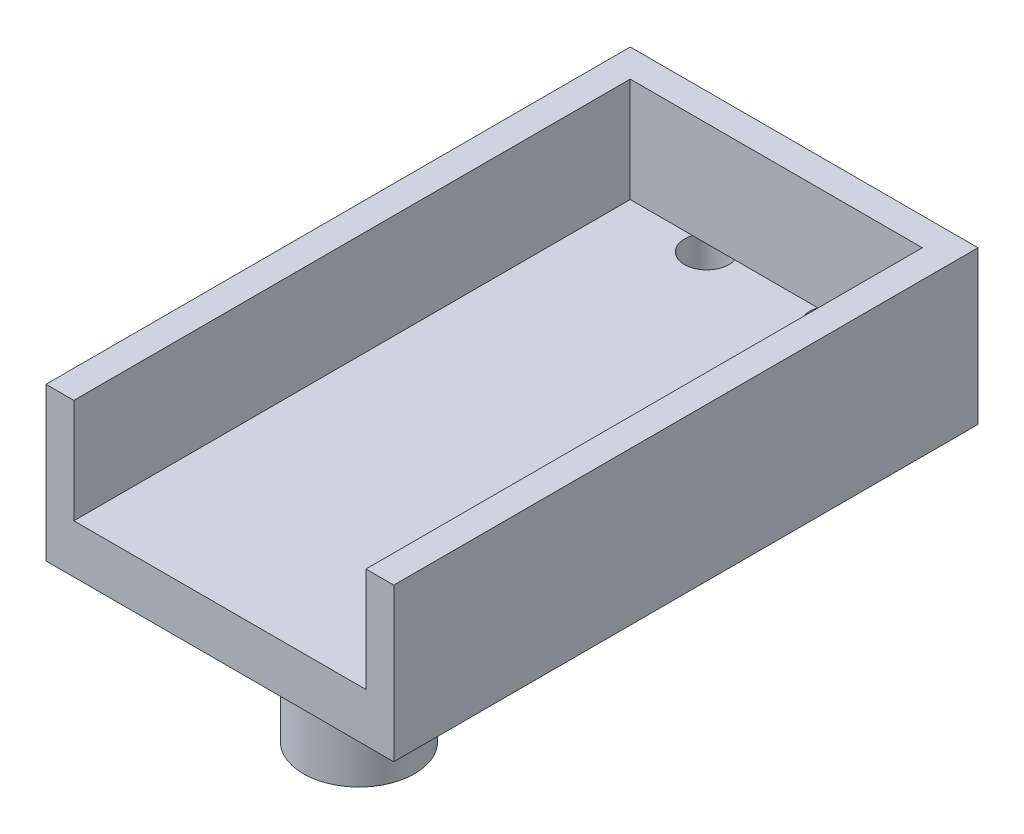
SolidWorks part; units mm, degrees
ref_plane "Front Plane" through (0, 0, 0) normal (0, 0, 1) x (1, 0, 0)
ref_plane "Top Plane" through (0, 0, 0) normal (0, 1, 0) x (1, 0, 0)
ref_plane "Right Plane" through (0, 0, 0) normal (1, 0, 0) x (0, 0, -1)
sketch "Sketch1" plane through (0, 0, 0) normal (0, 1, 0) x (1, 0, 0)
  line L1 (0, 40) -> (25, 40)
  line L2 (0, 40) -> (0, 0)
  line L3 (0, 0) -> (25, 0)
  line L4 (25, 40) -> (25, 0)
  dimension "D1" = 25
  dimension "D2" = 40
extrude "Boss-Extrude1" add sketch "Sketch1" along normal blind 3.5
sketch "Sketch2" plane through (0, 3.5, 0) normal (0, 1, 0) x (1, 0, 0)
  line L0 (25, 40) -> (0, 40) construction
  line L1 (0, 0) -> (2, 0)
  line L2 (0, 0) -> (0, 40)
  line L3 (0, 40) -> (2, 40)
  line L4 (2, 0) -> (2, 40)
  line L5 (0, 0) -> (25, 0) construction
  line L6 (25, 40) -> (23, 40)
  line L7 (25, 40) -> (25, 0)
  line L8 (25, 0) -> (23, 0)
  line L9 (23, 40) -> (23, 0)
  dimension "D1" = 2
  dimension "D2" = 2
extrude "Boss-Extrude2" add sketch "Sketch2" along normal blind 7.5
sketch "Sketch3" plane through (0, 0, 0) normal (0, -1, 0) x (-1, 0, 0)
  line L0 (0, 0) -> (-25, 0) construction
  circle A0 centre (-12.5, 10) radius 4
  point P2 (-12.5, 0)
  dimension "D1" = 8
  dimension "D2" = 10
extrude "Boss-Extrude3" add sketch "Sketch3" along normal blind 10
sketch "Sketch4" plane through (0, 0, -40) normal (0, 0, -1) x (-1, 0, 0)
  line L1 (-25, 11) -> (0, 11)
  line L2 (-25, 11) -> (-25, 0)
  line L3 (-25, 0) -> (0, 0)
  line L4 (0, 11) -> (0, 0)
extrude "Boss-Extrude4" add sketch "Sketch4" along normal blind 2 contours L1 L4 L3 L2
sketch "Sketch5" plane through (0, 0, 0) normal (0, -1, 0) x (1, 0, 0)
  line L0 (25, -42) -> (0, -42) construction
  circle A0 centre (8, -39.5) radius 1.6
  circle A1 centre (17, -39.5) radius 1.6
  point P7 (12.5, -42)
  dimension "D2" = 3.2
  dimension "D1" = 9
  dimension "D3" = 2.5
  dimension "D4" = 4.5
extrude "Cut-Extrude1" cut sketch "Sketch5" against normal up to surface (3.5 mm away) up to face at (12.5, 3.5, -20)
